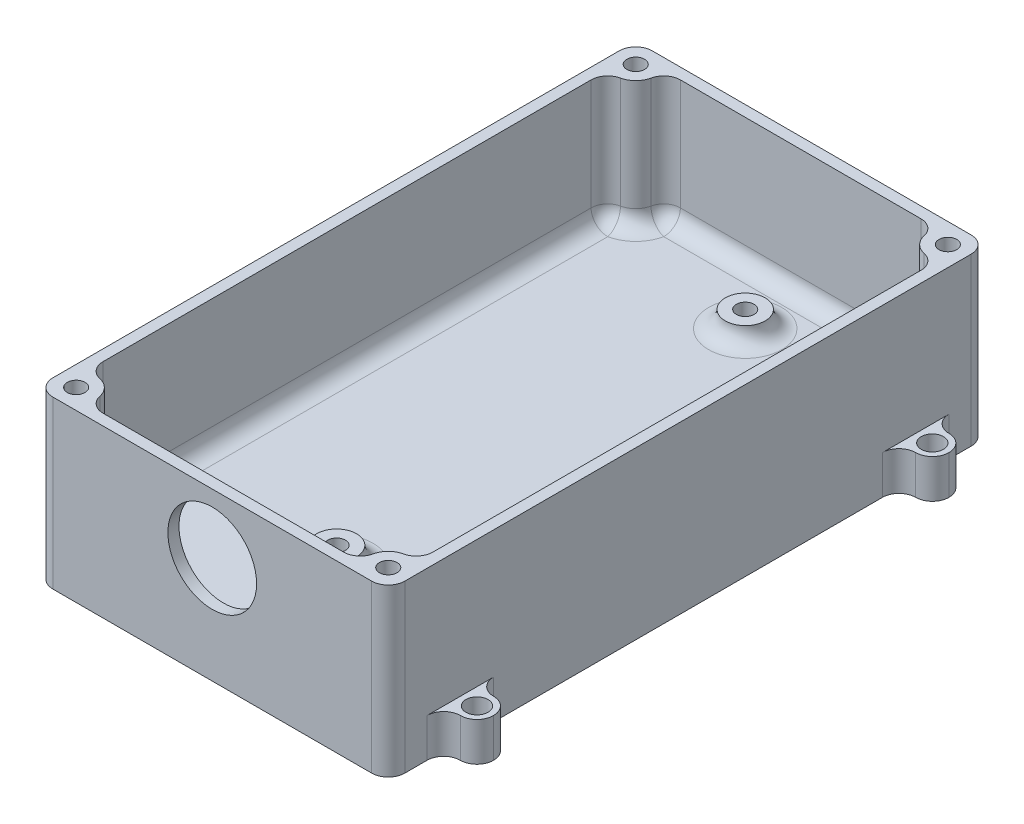
SolidWorks part; units mm, degrees
ref_plane "Front Plane" through (0, 0, 0) normal (0, 0, 1) x (1, 0, 0)
ref_plane "Top Plane" through (0, 0, 0) normal (0, 1, 0) x (1, 0, 0)
ref_plane "Right Plane" through (0, 0, 0) normal (1, 0, 0) x (0, 0, -1)
sketch "Sketch1" plane through (0, 0, 0) normal (0, 1, 0) x (1, 0, 0)
  line L0 (0, 52.07) -> (0, -52.07) construction
  line L1 (-24.9251, -52.07) -> (24.9251, -52.07)
  line L2 (-29.75, -47.2451) -> (-29.75, 47.2451)
  line L3 (-24.9251, 52.07) -> (24.9251, 52.07)
  line L4 (29.75, -47.2451) -> (29.75, 47.2451)
  line L5 (-31.75, 0) -> (31.75, 0) construction
  line L6 (-37.75, -38.07) -> (-31.75, -38.07)
  line L7 (31.75, -38.07) -> (37.75, -38.07)
  line L8 (-31.75, 54.07) -> (31.75, 54.07)
  line L9 (-31.75, 54.07) -> (-31.75, -54.07)
  line L10 (-31.75, -54.07) -> (31.75, -54.07)
  line L11 (31.75, 54.07) -> (31.75, -54.07)
  line L12 (31.75, -38.07) -> (31.75, -44.07)
  line L13 (31.75, -44.07) -> (37.75, -44.07)
  line L14 (37.75, -38.07) -> (37.75, -44.07)
  line L15 (31.75, -38.07) -> (37.75, -44.07) construction
  line L16 (31.75, -44.07) -> (37.75, -38.07) construction
  line L22 (31.75, 44.07) -> (37.75, 38.07) construction
  line L23 (31.75, 38.07) -> (37.75, 44.07) construction
  line L24 (37.75, 38.07) -> (37.75, 44.07)
  line L25 (31.75, 44.07) -> (37.75, 44.07)
  line L26 (31.75, 38.07) -> (31.75, 44.07)
  line L27 (31.75, 38.07) -> (37.75, 38.07)
  line L34 (-37.75, -38.07) -> (-37.75, -44.07)
  line L35 (-37.75, -44.07) -> (-31.75, -44.07)
  line L36 (-31.75, -38.07) -> (-31.75, -44.07)
  line L37 (-37.75, -38.07) -> (-31.75, -44.07) construction
  line L38 (-37.75, -44.07) -> (-31.75, -38.07) construction
  line L39 (31.75, 44.07) -> (37.75, 38.07) construction
  line L40 (31.75, 38.07) -> (37.75, 44.07) construction
  line L41 (37.75, 38.07) -> (37.75, 44.07)
  line L42 (31.75, 44.07) -> (37.75, 44.07)
  line L43 (31.75, 38.07) -> (31.75, 44.07)
  line L44 (31.75, 38.07) -> (37.75, 38.07)
  line L45 (-37.75, 44.07) -> (-31.75, 38.07) construction
  line L46 (-37.75, 38.07) -> (-31.75, 44.07) construction
  line L47 (-31.75, 38.07) -> (-31.75, 44.07)
  line L48 (-37.75, 44.07) -> (-31.75, 44.07)
  line L49 (-37.75, 38.07) -> (-37.75, 44.07)
  line L50 (-37.75, 38.07) -> (-31.75, 38.07)
  circle A0 centre (0, 42.07) radius 1.6
  circle A1 centre (0, -31.63) radius 1.6
  circle A2 centre (0, 42.07) radius 3.6
  circle A3 centre (0, -31.63) radius 3.6
  arc A4 (29.75, -47.2451) -> (24.9251, -52.07) centre (28.15, -50.47) ccw
  circle A5 centre (-28.15, 50.47) radius 1.6
  arc A6 (-29.75, 47.2451) -> (-24.9251, 52.07) centre (-28.15, 50.47) ccw
  circle A9 centre (-28.15, -50.47) radius 1.6
  arc A10 (-29.75, -47.2451) -> (-24.9251, -52.07) centre (-28.15, -50.47) cw
  circle A13 centre (34.75, -41.07) radius 2
  circle A15 centre (34.75, 41.07) radius 2
  circle A17 centre (-34.75, -41.07) radius 2
  circle A18 centre (34.75, 41.07) radius 2
  circle A19 centre (-34.75, 41.07) radius 2
  circle A20 centre (0, -31.63) radius 1.6 construction
  circle A21 centre (28.15, -50.47) radius 1.6
  arc A22 (29.75, 47.2451) -> (24.9251, 52.07) centre (28.15, 50.47) cw
  circle A23 centre (28.15, 50.47) radius 1.6
  point P20 (34.75, -41.07)
  point P27 (-34.75, -41.07)
  point P36 (34.75, 41.07)
  point P38 (34.75, 41.07)
  point P47 (-34.75, 41.07)
  dimension "D3" = 10
  dimension "D8" = 2
  dimension "D10" = 4
  dimension "D13" = 4
  dimension "D1" = 104.14
  dimension "D2" = 63.5
  dimension "D4" = 2
  dimension "D5" = 2
  dimension "D6" = 2
  dimension "D7" = 2
  dimension "D9" = 10
  dimension "D11" = 6
  dimension "D12" = 6
  dimension "D14" = 6
  dimension "D15" = 6
extrude "BASE" add sketch "Sketch1" along normal blind 7 contours L4 L3 A6 L2 A10 L1 A3 A2 | A5 | L9 L35 L34 L6 L10 L11 L8 A9 A5 L4 L1 A10 L2 A6 L3 | A3 A1 | A1 | A2 A0 | A0 | L14 L7 L11 L13 A13 | A9 | L9 L35 L36 L6 | L11 L27 L24 L25 A15 | L9 | A23 | A21 region at (0, 0, 0.0706) region at (-34.75, 0, 38.1549) region at (-30.4959, 0, 0) region at (-34.75, 0, -38.1549) region at (31.8349, 0, 41.07) region at (34.75, 0, -43.9851) region at (0, 0, -42.07) region at (0, 0, 31.63) region at (-3.4982, 0, -42.07) region at (-3.4982, 0, 31.63) region at (-28.15, 0, -50.47) region at (-28.15, 0, 50.47) region at (28.15, 0, 50.47) region at (28.15, 0, -50.47)
extrude "Walls" add sketch "Sketch1<3>" along normal blind 23 from surface contours L11 L8 L9 L10 L1 A10 L2 A6 L3 L4 A9 A5 region at (-30.4959, 0, 0) starting at face at (0, 7, 0)
sketch "Sketch1<3>" plane through (0, 0, 0) normal (0, 1, 0) x (1, 0, 0) same geometry as "Sketch1"
extrude "Standoffs" add sketch "Sketch1<4>" along normal blind 3 from surface contours A2 A0 | A3 A1 region at (-3.4982, 0, -42.07) region at (-3.4982, 0, 31.63) starting at face at (0, 7, 0)
sketch "Sketch1<4>" plane through (0, 0, 0) normal (0, 1, 0) x (1, 0, 0) same geometry as "Sketch1"
fillet "Internal Fillet" radius 3 18 edges at (0, 7, -38.47) (0, 7, 35.23) (0, 7, 52.07) (-25.6044, 7, 47.9244) (-24.9251, 18.5, 52.07) (-29.75, 18.5, 47.2451) (-29.75, 7, 0) (-25.6044, 7, -47.9244) (-24.9251, 18.5, -52.07) (-29.75, 18.5, -47.2451) (29.75, 7, 0) (0, 7, -52.07) (29.75, 18.5, 47.2451) (25.6044, 7, 47.9244) (24.9251, 18.5, 52.07) (24.9251, 18.5, -52.07) (25.6044, 7, -47.9244) (29.75, 18.5, -47.2451)
fillet "External Fillet" radius 3 20 edges at (-31.75, 15, 54.07) (-31.75, 15, -54.07) (31.75, 15, -54.07) (31.75, 15, 54.07) (31.75, 3.5, 38.07) (37.75, 3.5, 38.07) (37.75, 3.5, 44.07) (31.75, 3.5, 44.07) (31.75, 3.5, -38.07) (31.75, 3.5, -44.07) (37.75, 3.5, -38.07) (37.75, 3.5, -44.07) (-31.75, 3.5, -38.07) (-37.75, 3.5, -38.07) (-37.75, 3.5, -44.07) (-31.75, 3.5, -44.07) (-31.75, 3.5, 38.07) (-37.75, 3.5, 38.07) (-37.75, 3.5, 44.07) (-31.75, 3.5, 44.07)
sketch "Sketch2" plane through (27.4, 0, 54.07) normal (0, 0, -1) x (-1, 0, 0)
  line L3 (27.4, 30) -> (27.4, 0) construction
  line L4 (-1.35, 30) -> (56.15, 30) construction
  circle A0 centre (27.4, 19.2) radius 8
  point P6 (0, 0)
  dimension "D1" = 16
  dimension "D2" = 10.8
extrude "Cut-Extrude1" cut sketch "Sketch2" along normal up to surface (2 mm away) up to face at (0, 20, 52.07)
equation "\"D2@Sketch2\"=\"D1@Sketch2\"/2+2.8mm"
